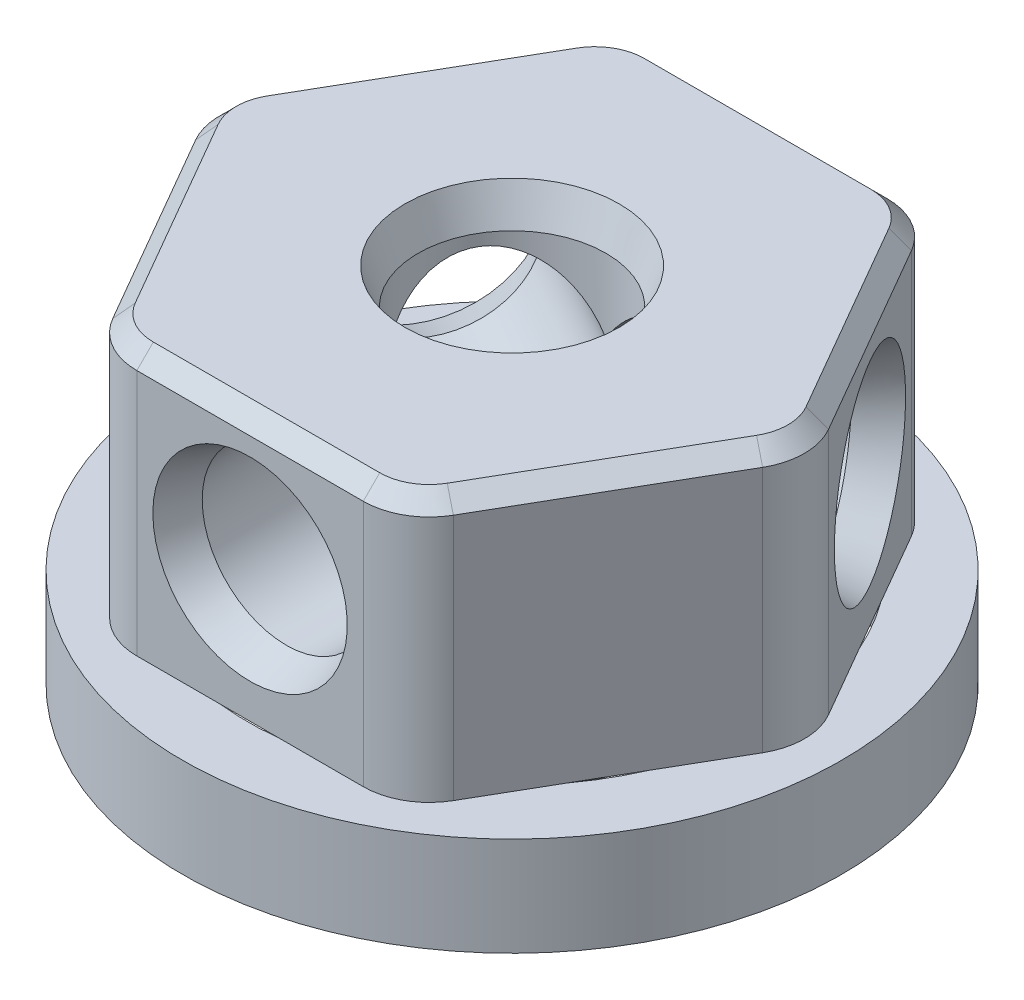
SolidWorks part; units mm, degrees
ref_plane "Front" through (0, 0, 0) normal (0, 0, 1) x (1, 0, 0)
ref_plane "Top" through (0, 0, 0) normal (0, 1, 0) x (1, 0, 0)
ref_plane "Right" through (0, 0, 0) normal (1, 0, 0) x (0, 0, -1)
sketch "Sketch1" plane through (0, 0, 0) normal (0, 1, 0) x (1, 0, 0)
  line L0 (0, 0) -> (0, 12.7) construction
  line L1 (0, 12.7) -> (-4.2426, 12.7) construction
  line L2 (-4.2426, 8.7) -> (4.2426, 8.7) construction
  line L3 (-4.5899, 7.95) -> (4.5899, 7.95)
  line L4 (9.1799, 0) -> (4.5899, -7.95)
  line L5 (-4.5899, -7.95) -> (-9.1799, 0)
  line L6 (-4.5899, 7.95) -> (-9.1799, 0)
  line L7 (-4.5899, -7.95) -> (4.5899, -7.95)
  line L8 (9.1799, 0) -> (4.5899, 7.95)
  circle A0 centre (0, 0) radius 2.85
  circle A1 centre (-4.2426, 12.7) radius 4 construction
  circle A2 centre (4.2426, 12.7) radius 4 construction
  point P11 (0, 8.7)
  point P12 (0, 2.85)
  point P15 (0, 7.95)
  point P21 (0, 0)
  dimension "D2" = 8
  dimension "D4" = 5.7
  dimension "D1" = 12.7
  dimension "D3" = 8.4853
  dimension "D5" = 5.85
  dimension "D6" = 1.5
  dimension "D7" = 3
extrude "Boss-Extrude1" add sketch "Sketch1" along normal blind 8
sketch "Sketch2" plane through (0, 0, 7.95) normal (0, 0, 1) x (1, 0, 0)
  line L0 (0, 0) -> (0, 8) construction
  line L1 (-4.5899, 8) -> (4.5899, 8) construction
  circle A0 centre (0, 4) radius 2.55
  point P5 (0, 4)
  dimension "D1" = 5.1
extrude "Cut-Extrude1" cut sketch "Sketch2" against normal up to next
pattern_circular "CirPattern1" count 3 over 360 about axis through (0, 8, 0) along (0, -1, 0) of "Cut-Extrude1"
chamfer "Chamfer1" distance 0.4 angle 70 4 edges at (0, 8, 2.85) (-8.1599, 4, -1.7666) (5.6099, 4, -6.1834) (2.55, 4, 7.95) first distance on face at (0, 8, 0) first distance on face at (-8.1599, 4, -1.7666) first distance on face at (5.6099, 4, -6.1834) first distance on face at (2.55, 4, 7.95)
fillet "Fillet1" radius 2 6 edges at (-9.1799, 4, 0) (-4.5899, 4, 7.95) (4.5899, 4, 7.95) (9.1799, 4, 0) (-4.5899, 4, -7.95) (4.5899, 4, -7.95)
sketch "Sketch3" plane through (0, 0, 0) normal (0, -1, 0) x (1, 0, 0)
  circle A0 centre (0, 0) radius 10
  dimension "D1" = 20
extrude "Boss-Extrude2" add sketch "Sketch3" along normal blind 3
sketch "Sketch4" plane through (0, -3, 0) normal (0, -1, 0) x (1, 0, 0)
  circle A0 centre (0, 0) radius 7
  circle A1 centre (0, 0) radius 8
  dimension "D1" = 14
  dimension "D2" = 16
extrude "Cut-Extrude2" cut sketch "Sketch4" against normal blind 3
chamfer "Chamfer3" distance 3 angle 45 1 edges at (0, -3, -7)
chamfer "Chamfer2" distance 0.5 angle 45 12 edges at (-6.8849, 8, 3.975) (-6.8849, 8, -3.975) (0, 8, -7.95) (6.8849, 8, -3.975) (6.8849, 8, 3.975) (0, 8, 7.95) (-4.4352, 8, -7.6821) (4.4352, 8, -7.6821) (-8.8705, 8, 0) (8.8705, 8, 0) (-4.4352, 8, 7.6821) (4.4352, 8, 7.6821)
